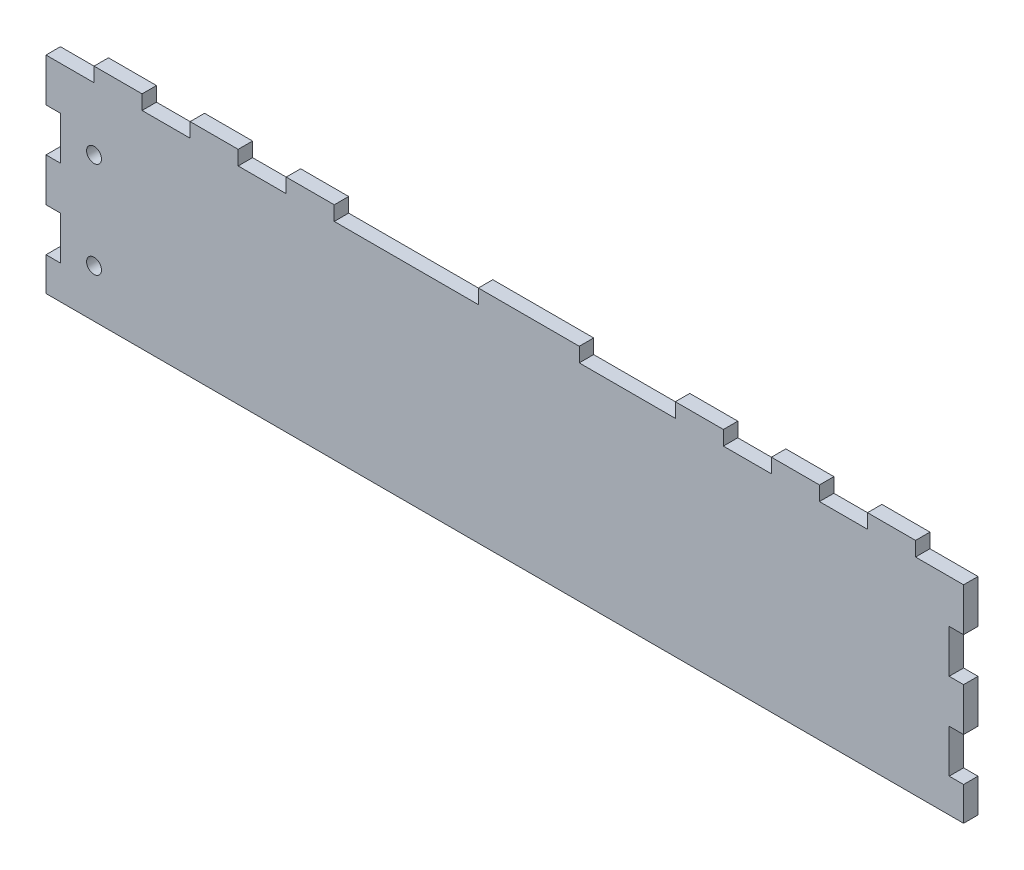
SolidWorks part; units mm, degrees
ref_plane "Front Plane" through (0, 0, 0) normal (0, 0, 1) x (1, 0, 0)
ref_plane "Top Plane" through (0, 0, 0) normal (0, 1, 0) x (1, 0, 0)
ref_plane "Right Plane" through (0, 0, 0) normal (1, 0, 0) x (0, 0, -1)
sketch "Sketch1" plane through (0, 0, 0) normal (0, 0, 1) x (1, 0, 0)
  line L4 (-191, 0) -> (0, 0)
  line L5 (0, 0) -> (0, 46)
  line L6 (0, 46) -> (-191, 46)
  line L7 (-191, 46) -> (-191, 0)
  line L8 (-191, 0) -> (0, 0)
  line L9 (0, 0) -> (0, 46)
  line L10 (0, 46) -> (-191, 46)
  line L11 (-191, 46) -> (-191, 0)
  circle A0 centre (-181, 30) radius 1.55 construction
  circle A1 centre (-181, 10) radius 1.55 construction
  circle A2 centre (-181, 30) radius 1.55
  circle A3 centre (-181, 10) radius 1.55
  dimension "D1" = 0
extrude "Boss-Extrude1" add sketch "Sketch1" along normal blind 3
sketch "Sketch5" plane through (0, 0, 3) normal (0, 0, 1) x (1, 0, 0)
  line L0 (-95.5, 0) -> (-95.5, 46) construction
  line L1 (-191, 0) -> (0, 0) construction
  line L2 (0, 46) -> (-191, 46) construction
ref_axis "Axis1" through (-95.5, 0, 3) along (0, 1, 0)
ref_plane "Plane1" through (-95.5, 0, 0) normal (1, 0, 0) x (0, 1, 0)
sketch "Sketch2" plane through (0, 0, 3) normal (0, 0, 1) x (1, 0, 0)
  line L0 (-119.5, 46) -> (-119.5, 0) construction
  line L1 (-119.5, 46) -> (-119.5, 0)
  point P2 (-119.5, 23)
ref_point "MointPoint-Sus"
sketch "Sketch3" plane through (0, 0, 0) normal (0, 0, -1) x (-1, 0, 0)
  line L4 (50, 43) -> (50, 46)
  line L5 (50, 46) -> (40, 46)
  line L6 (40, 46) -> (40, 43)
  line L7 (40, 43) -> (50, 43)
  line L8 (50, 43) -> (50, 46)
  line L9 (50, 46) -> (40, 46)
  line L10 (40, 46) -> (40, 43)
  line L11 (40, 43) -> (50, 43)
  line L12 (30, 43) -> (30, 46)
  line L13 (30, 46) -> (20, 46)
  line L14 (20, 46) -> (20, 43)
  line L15 (20, 43) -> (30, 43)
  line L16 (30, 43) -> (30, 46)
  line L17 (30, 46) -> (20, 46)
  line L18 (20, 46) -> (20, 43)
  line L19 (20, 43) -> (30, 43)
  line L20 (10, 43) -> (10, 46)
  line L21 (10, 46) -> (0, 46)
  line L22 (0, 46) -> (0, 43)
  line L23 (0, 43) -> (10, 43)
  line L24 (10, 43) -> (10, 46)
  line L25 (10, 46) -> (0, 46)
  line L26 (0, 46) -> (0, 43)
  line L27 (0, 43) -> (10, 43)
  line L28 (171, 43) -> (171, 46)
  line L29 (171, 46) -> (161, 46)
  line L30 (161, 46) -> (161, 43)
  line L31 (161, 43) -> (171, 43)
  line L32 (171, 43) -> (171, 46)
  line L33 (171, 46) -> (161, 46)
  line L34 (161, 46) -> (161, 43)
  line L35 (161, 43) -> (171, 43)
  line L36 (151, 43) -> (151, 46)
  line L37 (151, 46) -> (141, 46)
  line L38 (141, 46) -> (141, 43)
  line L39 (141, 43) -> (151, 43)
  line L40 (151, 43) -> (151, 46)
  line L41 (151, 46) -> (141, 46)
  line L42 (141, 46) -> (141, 43)
  line L43 (141, 43) -> (151, 43)
  line L44 (131, 46) -> (101, 46)
  line L45 (101, 46) -> (101, 43)
  line L46 (101, 43) -> (131, 43)
  line L47 (131, 43) -> (131, 46)
  line L48 (131, 46) -> (101, 46)
  line L49 (101, 46) -> (101, 43)
  line L50 (101, 43) -> (131, 43)
  line L51 (131, 43) -> (131, 46)
  line L52 (80, 46) -> (60, 46)
  line L53 (80, 43) -> (80, 46)
  line L54 (60, 43) -> (80, 43)
  line L55 (60, 46) -> (60, 43)
  line L56 (80, 46) -> (60, 46)
  line L57 (80, 43) -> (80, 46)
  line L58 (60, 43) -> (80, 43)
  line L59 (60, 46) -> (60, 43)
  line L60 (181, 43) -> (191, 43)
  line L61 (181, 46) -> (181, 43)
  line L62 (191, 46) -> (181, 46)
  line L63 (191, 43) -> (191, 46)
  line L64 (181, 43) -> (191, 43)
  line L65 (181, 46) -> (181, 43)
  line L66 (191, 46) -> (181, 46)
  line L67 (191, 43) -> (191, 46)
  dimension "D1" = 0
  dimension "D2" = 0
  dimension "D3" = 0
  dimension "D4" = 0
  dimension "D5" = 0
  dimension "D6" = 0
  dimension "D7" = 0
  dimension "D8" = 0
extrude "Cut-Extrude1" cut sketch "Sketch3" against normal up to next
sketch "Sketch4" plane through (0, 0, 3) normal (0, 0, 1) x (1, 0, 0)
  line L0 (-3, 43) -> (-3, 0) construction
  line L1 (0, 43) -> (-10, 43) construction
  line L2 (-191, 0) -> (0, 0) construction
  line L3 (0, 0) -> (0, 43) construction
  line L4 (-3, 34) -> (0, 34)
  line L5 (-3, 25) -> (0, 25)
  line L6 (-3, 16) -> (0, 16)
  line L7 (-3, 7) -> (0, 7)
  line L8 (0, 34) -> (0, 25)
  line L9 (-3, 25) -> (-3, 34)
  line L10 (0, 16) -> (0, 7)
  line L11 (-3, 7) -> (-3, 16)
  dimension "D1" = 3
  dimension "D2" = 9
  dimension "D3" = 4
extrude "Cut-Extrude2" cut sketch "Sketch4" against normal up to next
mirror "Mirror1" about plane through (-95.5, 0, 0) normal (1, 0, 0) of "Cut-Extrude2"
